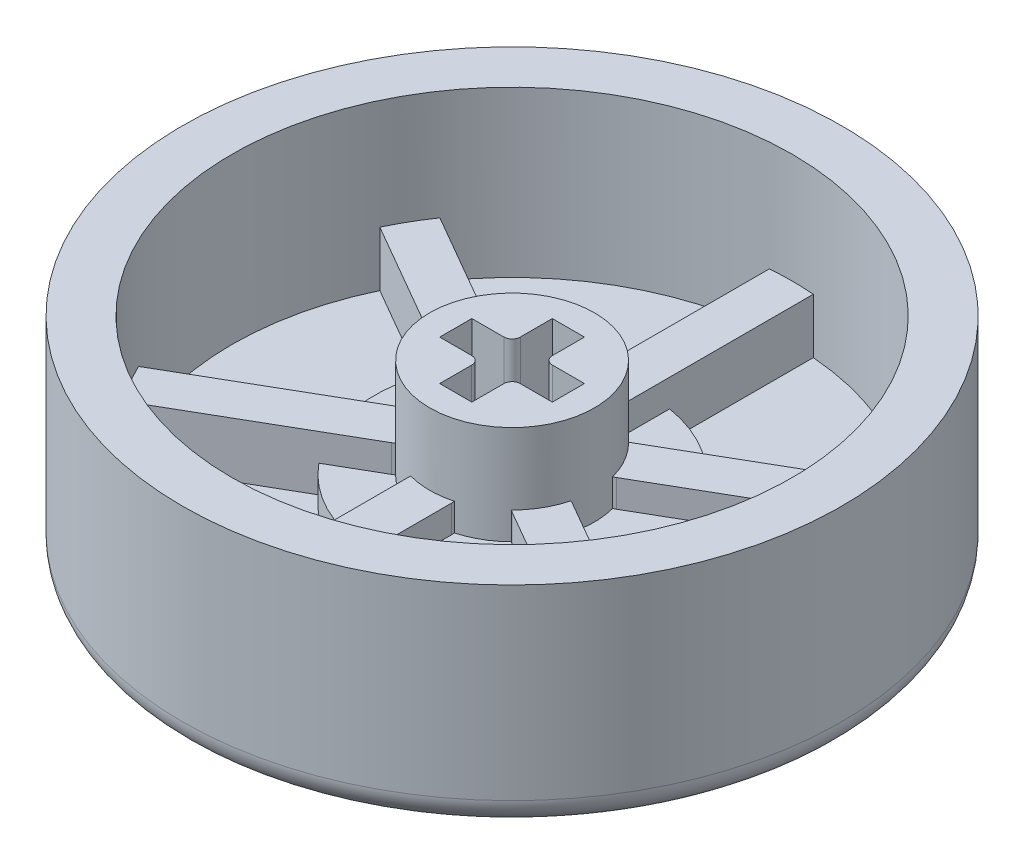
SolidWorks part; units mm, degrees
ref_plane "Front Plane" through (0, 0, 0) normal (0, 0, 1) x (1, 0, 0)
ref_plane "Top Plane" through (0, 0, 0) normal (0, 1, 0) x (1, 0, 0)
ref_plane "Right Plane" through (0, 0, 0) normal (1, 0, 0) x (0, 0, -1)
sketch "Sketch1" plane through (0, 0, 0) normal (0, 1, 0) x (1, 0, 0)
  circle A0 centre (0, 0) radius 12
  dimension "D1" = 24
extrude "button top" add sketch "Sketch1" along normal blind 1.8
sketch "Sketch2" plane through (0, 1.8, 0) normal (0, 1, 0) x (1, 0, 0)
  circle A3 centre (0, 0) radius 12
  circle A4 centre (0, 0) radius 12 construction
  circle A5 centre (0, 0) radius 10.2
  dimension "D1" = 1.8
extrude "button walls" add sketch "Sketch2" along normal blind 6
sketch "Sketch5" plane through (0, 1.8, 0) normal (0, 1, 0) x (1, 0, 0)
  circle A0 centre (0, 0) radius 5
  dimension "D1" = 10
extrude "offset" add sketch "Sketch5" along normal blind 1
sketch "Sketch3" plane through (0, 1.8, 0) normal (0, 1, 0) x (1, 0, 0)
  line L0 (0, -2.05) -> (0, 2.05) construction
  line L1 (-2.05, 0) -> (2.05, 0) construction
  line L2 (-0.585, 0.885) -> (-0.585, 2.05)
  line L3 (-0.585, -2.05) -> (0.585, -2.05)
  line L4 (-0.585, -2.05) -> (-0.585, -0.885)
  line L5 (-0.585, 2.05) -> (0.585, 2.05)
  line L6 (0.585, -2.05) -> (0.585, -0.885)
  line L7 (-0.585, -2.05) -> (0.585, 2.05) construction
  line L8 (-0.585, 2.05) -> (0.585, -2.05) construction
  line L9 (-2.05, -0.585) -> (-0.885, -0.585)
  line L10 (-2.05, -0.585) -> (-2.05, 0.585)
  line L11 (-2.05, 0.585) -> (-0.885, 0.585)
  line L12 (2.05, -0.585) -> (2.05, 0.585)
  line L13 (-2.05, -0.585) -> (2.05, 0.585) construction
  line L14 (-2.05, 0.585) -> (2.05, -0.585) construction
  line L15 (0.885, 0.585) -> (2.05, 0.585)
  line L16 (0.585, 0.885) -> (0.585, 2.05)
  line L17 (0.885, -0.585) -> (2.05, -0.585)
  circle A0 centre (0, 0) radius 3
  arc A1 (-0.585, -0.885) -> (-0.885, -0.585) centre (-0.885, -0.885) ccw
  arc A2 (0.585, -0.885) -> (0.885, -0.585) centre (0.885, -0.885) cw
  arc A3 (0.885, 0.585) -> (0.585, 0.885) centre (0.885, 0.885) cw
  arc A4 (-0.585, 0.885) -> (-0.885, 0.585) centre (-0.885, 0.885) cw
  point P6 (0, 0)
  point P9 (0, 0)
  point P22 (2.05, 0)
  point P24 (0, 2.05)
  point P29 (0.585, -0.585)
  point P32 (0.585, 0.585)
  dimension "D1" = 6
  dimension "D4" = 0.3
  dimension "D2" = 4.1
  dimension "D3" = 1.17
extrude "stem housing" add sketch "Sketch3" along normal blind 3.6 from surface starting at face at (0, 2.8, 5)
sketch "Sketch4" plane through (0, 1.8, 0) normal (0, 1, 0) x (1, 0, 0)
  line L0 (0, 3) -> (0, 10.2) construction
  line L1 (-0.8, 3) -> (-0.8, 10.2)
  line L2 (0.8, 3) -> (0.8, 10.2)
  line L3 (2.5981, 1.5) -> (8.8335, 5.1) construction
  line L4 (2.1981, 2.1928) -> (8.4335, 5.7928)
  line L5 (2.9981, 0.8072) -> (9.2335, 4.4072)
  line L6 (2.5981, -1.5) -> (8.8335, -5.1) construction
  line L7 (2.9981, -0.8072) -> (9.2335, -4.4072)
  line L8 (2.1981, -2.1928) -> (8.4335, -5.7928)
  line L9 (0, -3) -> (0, -10.2) construction
  line L10 (0.8, -3) -> (0.8, -10.2)
  line L11 (-0.8, -3) -> (-0.8, -10.2)
  line L12 (-2.5981, -1.5) -> (-8.8335, -5.1) construction
  line L13 (-2.1981, -2.1928) -> (-8.4335, -5.7928)
  line L14 (-2.9981, -0.8072) -> (-9.2335, -4.4072)
  line L15 (-2.5981, 1.5) -> (-8.8335, 5.1) construction
  line L16 (-2.9981, 0.8072) -> (-9.2335, 4.4072)
  line L17 (-2.1981, 2.1928) -> (-8.4335, 5.7928)
  circle A0 centre (0, 0) radius 3 construction
  circle A1 centre (0, 0) radius 3 construction
  circle A2 centre (0, 0) radius 10.2 construction
  arc A3 (-0.8, 3) -> (0.8, 3) centre (0, 3) ccw
  arc A4 (0.8, 10.2) -> (-0.8, 10.2) centre (0, 10.2) ccw
  arc A5 (2.1981, 2.1928) -> (2.9981, 0.8072) centre (2.5981, 1.5) ccw
  arc A6 (9.2335, 4.4072) -> (8.4335, 5.7928) centre (8.8335, 5.1) ccw
  arc A7 (2.9981, -0.8072) -> (2.1981, -2.1928) centre (2.5981, -1.5) ccw
  arc A8 (8.4335, -5.7928) -> (9.2335, -4.4072) centre (8.8335, -5.1) ccw
  arc A9 (0.8, -3) -> (-0.8, -3) centre (0, -3) ccw
  arc A10 (-0.8, -10.2) -> (0.8, -10.2) centre (0, -10.2) ccw
  arc A11 (-2.1981, -2.1928) -> (-2.9981, -0.8072) centre (-2.5981, -1.5) ccw
  arc A12 (-9.2335, -4.4072) -> (-8.4335, -5.7928) centre (-8.8335, -5.1) ccw
  arc A13 (-2.9981, 0.8072) -> (-2.1981, 2.1928) centre (-2.5981, 1.5) ccw
  arc A14 (-8.4335, 5.7928) -> (-9.2335, 4.4072) centre (-8.8335, 5.1) ccw
  point P9 (0, 6.6)
  point P18 (5.7158, 3.3)
  point P25 (5.7158, -3.3)
  point P32 (0, -6.6)
  point P39 (-5.7158, -3.3)
  point P46 (-5.7158, 3.3)
  point P51 (0, 0)
  dimension "D1" = 1.6
  dimension "D2" = 6
extrude "Boss-Extrude4" add sketch "Sketch4" along normal blind 2
fillet "Fillet1" radius 1 1 edges at (0, 0, 12)
